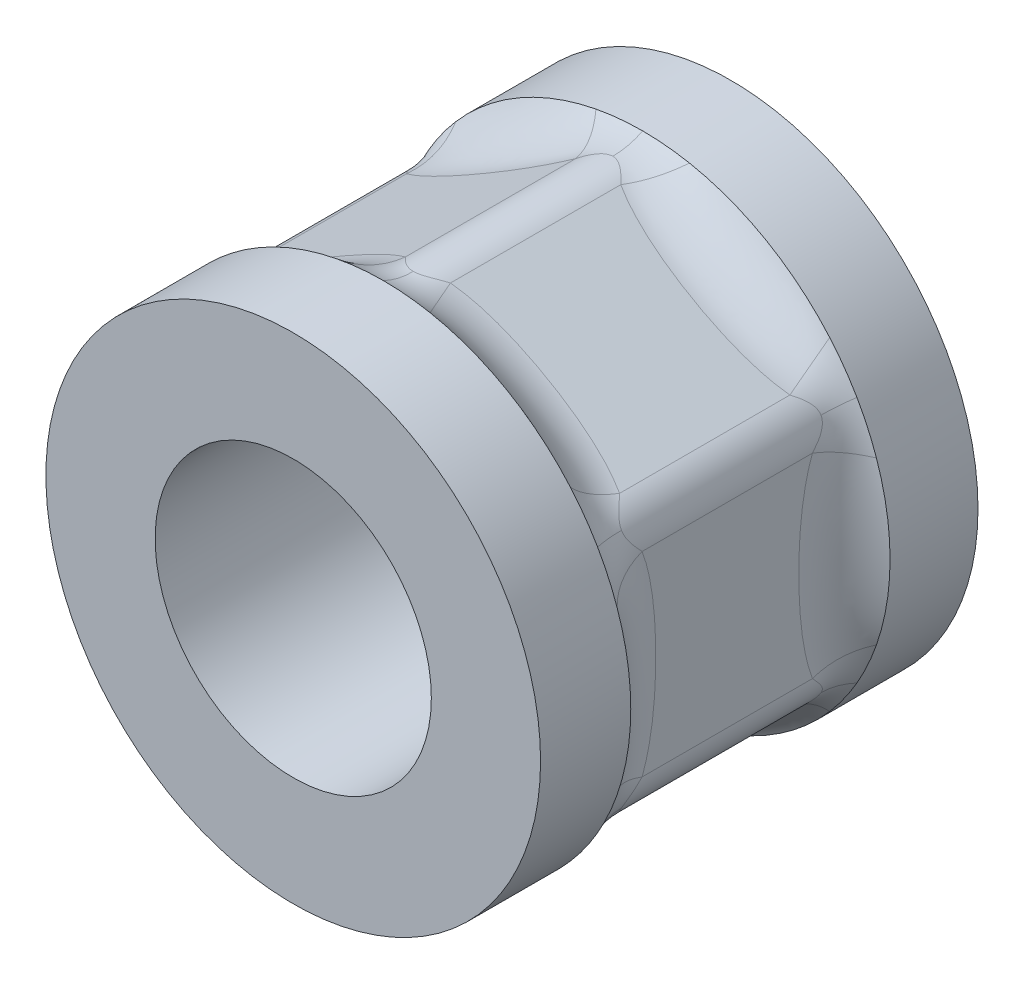
SolidWorks part; units mm, degrees
ref_plane "Front Plane" through (0, 0, 0) normal (0, 0, 1) x (1, 0, 0)
ref_plane "Top Plane" through (0, 0, 0) normal (0, 1, 0) x (1, 0, 0)
ref_plane "Right Plane" through (0, 0, 0) normal (1, 0, 0) x (0, 0, -1)
sketch "Sketch1" plane through (0, 0, 0) normal (0, 0, 1) x (1, 0, 0)
  line L1 (0, -7.5633) -> (6.55, -3.7816)
  line L2 (6.55, -3.7816) -> (6.55, 3.7816)
  line L3 (6.55, 3.7816) -> (0, 7.5633)
  line L4 (0, 7.5633) -> (-6.55, 3.7816)
  line L5 (-6.55, 3.7816) -> (-6.55, -3.7816)
  line L6 (-6.55, -3.7816) -> (0, -7.5633)
  line L7 (0, -10.9697) -> (9.5, -5.4848) construction
  line L8 (9.5, -5.4848) -> (9.5, 5.4848) construction
  line L9 (9.5, 5.4848) -> (0, 10.9697) construction
  line L10 (0, 10.9697) -> (-9.5, 5.4848) construction
  line L11 (-9.5, 5.4848) -> (-9.5, -5.4848) construction
  line L12 (-9.5, -5.4848) -> (0, -10.9697) construction
  circle A0 centre (0, 0) radius 6.55 construction
  circle A1 centre (0, 0) radius 10.9697
  circle A2 centre (0, 0) radius 9.5 construction
  point P1 (0, 0)
  point P18 (-1.0956, 10.9148)
  point P19 (0, 0)
  dimension "D1" = 13.1
  dimension "D2" = 19
extrude "Boss-Extrude1" add sketch "Sketch1" along normal blind 6.4
sketch "Sketch2" plane through (0, 0, 6.4) normal (0, 0, 1) x (1, 0, 0)
  circle A0 centre (0, 0) radius 6.125
  circle A2 centre (0, 0) radius 10.9697 construction
  circle A3 centre (0, 0) radius 10.9697
  dimension "D1" = 12.25
extrude "Boss-Extrude2" add sketch "Sketch2" along normal blind 10 contours A3 | A0
sketch "Sketch3" plane through (0, 0, 0) normal (0, 0, -1) x (-1, 0, 0)
  circle A0 centre (0, 0) radius 4
  circle A1 centre (0, 0) radius 10.9697 construction
  circle A2 centre (0, 0) radius 10.9697
  dimension "D1" = 8
extrude "Boss-Extrude3" add sketch "Sketch3" along normal blind 3
sketch "Sketch4" plane through (0, 0, 0) normal (0, 0, 1) x (1, 0, 0)
  circle A0 centre (0, 0) radius 4 construction
  circle A1 centre (0, 0) radius 4
extrude "Boss-Extrude4" add sketch "Sketch4" against normal blind 0.6
sketch "Sketch5" plane through (0, 0, 6.4) normal (0, 0, -1) x (-1, 0, 0)
  line L1 (9.5, 5.4848) -> (0, 10.9697)
  line L2 (0, 10.9697) -> (-9.5, 5.4848)
  line L3 (-9.5, 5.4848) -> (-9.5, -5.4848)
  line L4 (-9.5, -5.4848) -> (0, -10.9697)
  line L5 (0, -10.9697) -> (9.5, -5.4848)
  line L6 (9.5, -5.4848) -> (9.5, 5.4848)
  circle A0 centre (0, 0) radius 9.5 construction
  circle A1 centre (0, 0) radius 10.9697 construction
  circle A2 centre (0, 0) radius 10.9697
  point P1 (2.3027, 11.5517)
extrude "Cut-Extrude1" cut sketch "Sketch5" against normal blind 6 and the other way blind 5.5 contours L3 A2 | L2 A2 | L1 A2 | L5 A2 | L4 A2 | L6 A2 region at (-10.0914, 0, 6.4) region at (-5.0457, 8.7394, 6.4) region at (5.0457, 8.7394, 6.4) region at (-5.0457, -8.7394, 6.4) region at (10.0914, 0, 6.4) region at (5.0457, -8.7394, 6.4)
fillet "Fillet4" radius 2 6 edges at (9.5, 5.4848, 6.65) (9.5, -5.4848, 6.65) (0, -10.9697, 6.65) (0, 10.9697, 6.65) (-9.5, 5.4848, 6.65) (-9.5, -5.4848, 6.65)
fillet "Fillet5" radius 3 12 edges at (4.75, 8.2272, 12.4) (-4.75, 8.2272, 12.4) (-9.5, 0, 12.4) (-4.75, -8.2272, 12.4) (4.75, -8.2272, 12.4) (9.5, 0, 12.4) (-4.75, 8.2272, 0.9) (-9.5, 0, 0.9) (-4.75, -8.2272, 0.9) (4.75, -8.2272, 0.9) (9.5, 0, 0.9) (4.75, 8.2272, 0.9)
